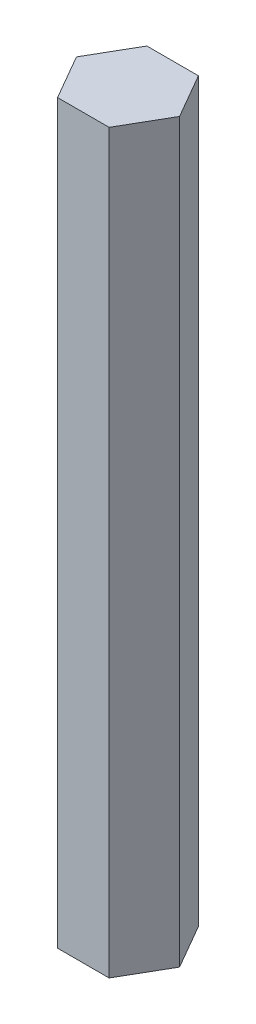
SolidWorks part; units mm, degrees
material "6061 Alloy"
ref_plane "Front Plane" through (0, 0, 0) normal (0, 0, 1) x (1, 0, 0)
ref_plane "Top Plane" through (0, 0, 0) normal (0, 1, 0) x (1, 0, 0)
ref_plane "Right Plane" through (0, 0, 0) normal (1, 0, 0) x (0, 0, -1)
sketch "Sketch1" plane through (0, 0, 0) normal (0, 1, 0) x (1, 0, 0)
  line L1 (7.3323, 0) -> (3.6662, 6.35)
  line L2 (3.6662, 6.35) -> (-3.6662, 6.35)
  line L3 (-3.6662, 6.35) -> (-7.3323, 0)
  line L4 (-7.3323, 0) -> (-3.6662, -6.35)
  line L5 (-3.6662, -6.35) -> (3.6662, -6.35)
  line L6 (3.6662, -6.35) -> (7.3323, 0)
  circle A0 centre (0, 0) radius 6.35 construction
extrude "Boss-Extrude1" add sketch "Sketch1" along normal blind 104.775 contours L2 L3 L4 L5 L6 L1
ref_axis "Axis1" through (0, -8.255, 0) along (0, 1, 0)
